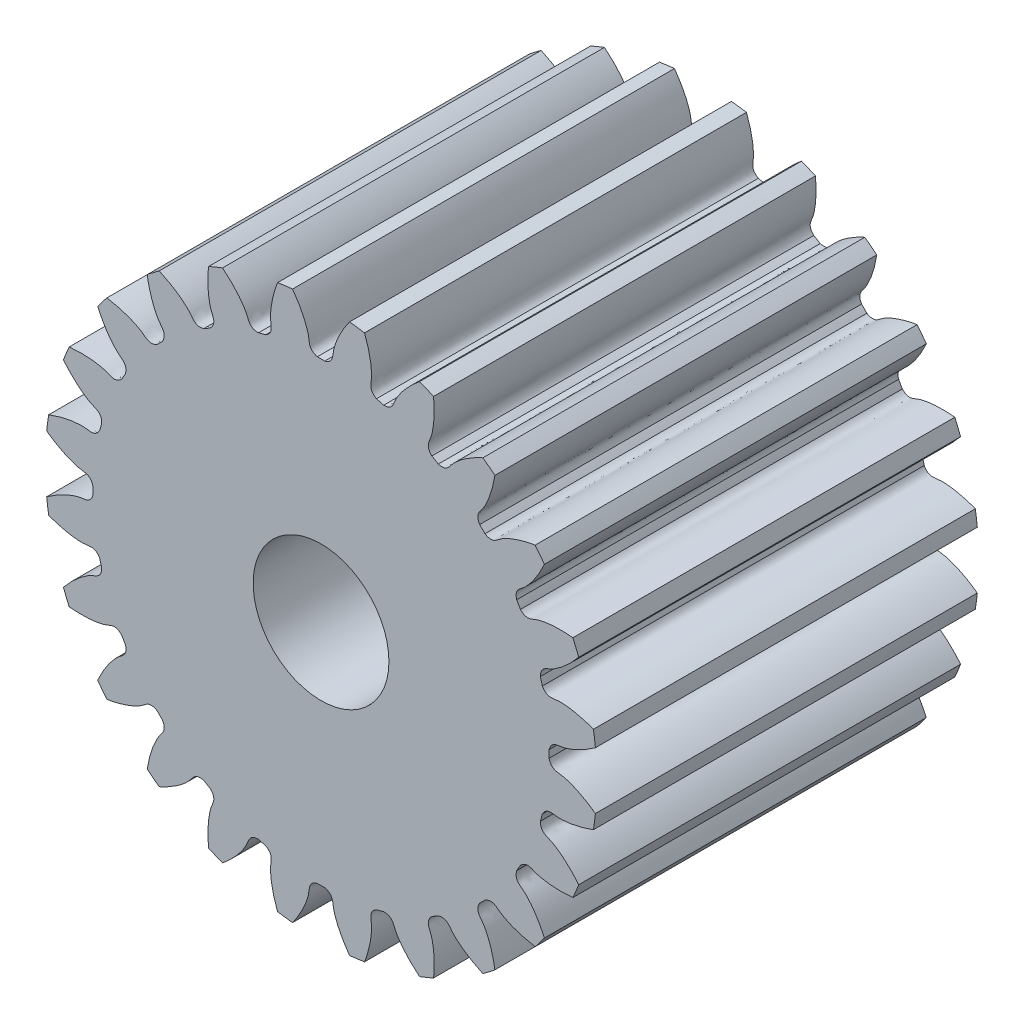
SolidWorks part; units mm, degrees
ref_plane "前视基准面" through (0, 0, 0) normal (0, 0, 1) x (1, 0, 0)
ref_plane "上视基准面" through (0, 0, 0) normal (0, 1, 0) x (1, 0, 0)
ref_plane "右视基准面" through (0, 0, 0) normal (1, 0, 0) x (0, 0, -1)
sketch "草图1" plane through (0, 0, 0) normal (0, 0, 1) x (1, 0, 0)
  circle A0 centre (0, 0) radius 6.5
extrude "凸台-拉伸1" add sketch "草图1" along normal blind 9
ref_axis "基准轴1" through (0, 0, 9) along (0, 0, -1)
sketch "草图2" plane through (0, 0, 0) normal (0, 0, 1) x (1, 0, 0)
  line L0 (0, 0) -> (0, 6.5) construction
  circle A0 centre (0, 0) radius 6.5 construction
  arc A1 (0.0884, 5.3743) -> (-0.0884, 5.3743) centre (0, 0) ccw
  arc A2 (1.5578, 7.3471) -> (-1.5578, 7.3471) centre (0, 0) ccw
  spline S0 degree 3 poles (0.0884, 5.3743) (0.284, 5.4284) (0.2695, 5.5579) (0.2931, 5.6863) (0.2965, 5.7029) (0.3007, 5.7216) (0.3058, 5.7424) (0.312, 5.7653) (0.3191, 5.7902) (0.3275, 5.8171) (0.3371, 5.846) (0.348, 5.8769) (0.3604, 5.9096) (0.3742, 5.9441) (0.3896, 5.9805) (0.4067, 6.0185) (0.4254, 6.0583) (0.446, 6.0997) (0.4684, 6.1427) (0.4928, 6.1872) (0.5192, 6.2332) (0.5476, 6.2806) (0.5782, 6.3293) (0.611, 6.3792) (0.6461, 6.4304) (0.6834, 6.4827) (0.7232, 6.536) (0.7654, 6.5903) (0.8101, 6.6456) (0.8574, 6.7016) (0.9073, 6.7583) (0.9598, 6.8158) (1.015, 6.8738) (1.0729, 6.9322) (1.1336, 6.9911) (1.1972, 7.0503) (1.2635, 7.1097) (1.3328, 7.1693) (1.4302, 7.2497) (1.506, 7.3084) (1.5578, 7.3471) knots 0 0 0 0 0.143961 0.149818 0.156577 0.164236 0.172796 0.182258 0.19262 0.203884 0.216049 0.229115 0.243082 0.25795 0.273719 0.290389 0.30796 0.326433 0.345806 0.366081 0.387257 0.409333 0.432311 0.45619 0.48097 0.506651 0.533234 0.560717 0.589101 0.618387 0.648574 0.679661 0.71165 0.74454 0.778331 0.813023 0.848616 0.885111 0.922506 1 1 1 1
  spline S1 degree 3 poles (-0.0884, 5.3743) (-0.284, 5.4284) (-0.2695, 5.5579) (-0.2931, 5.6863) (-0.2965, 5.7029) (-0.3007, 5.7216) (-0.3058, 5.7424) (-0.312, 5.7653) (-0.3191, 5.7902) (-0.3275, 5.8171) (-0.3371, 5.846) (-0.348, 5.8769) (-0.3604, 5.9096) (-0.3742, 5.9441) (-0.3896, 5.9805) (-0.4067, 6.0185) (-0.4254, 6.0583) (-0.446, 6.0997) (-0.4684, 6.1427) (-0.4928, 6.1872) (-0.5192, 6.2332) (-0.5476, 6.2806) (-0.5782, 6.3293) (-0.611, 6.3792) (-0.6461, 6.4304) (-0.6834, 6.4827) (-0.7232, 6.536) (-0.7654, 6.5903) (-0.8101, 6.6456) (-0.8574, 6.7016) (-0.9073, 6.7583) (-0.9598, 6.8158) (-1.015, 6.8738) (-1.0729, 6.9322) (-1.1336, 6.9911) (-1.1972, 7.0503) (-1.2635, 7.1097) (-1.3328, 7.1693) (-1.4302, 7.2497) (-1.506, 7.3084) (-1.5578, 7.3471) knots 0 0 0 0 0.143961 0.149818 0.156577 0.164236 0.172796 0.182258 0.19262 0.203884 0.216049 0.229115 0.243082 0.25795 0.273719 0.290389 0.30796 0.326433 0.345806 0.366081 0.387257 0.409333 0.432311 0.45619 0.48097 0.506651 0.533234 0.560717 0.589101 0.618387 0.648574 0.679661 0.71165 0.74454 0.778331 0.813023 0.848616 0.885111 0.922506 1 1 1 1
extrude "切除-拉伸1" cut sketch "草图2" along normal through all
pattern_circular "阵列(圆周)1" count 24 every 15 about axis through (0, 0, 9) along (0, 0, -1) of "切除-拉伸1"
sketch "草图3" plane through (0, 0, 0) normal (0, 0, 1) x (1, 0, 0)
  circle A0 centre (0, 0) radius 6 construction
  dimension "Dn" = 12
sketch "草图4" plane through (0, 0, 9) normal (0, 0, 1) x (1, 0, 0)
  circle A0 centre (0, 0) radius 1.6
  dimension "D1" = 3.2
extrude "切除-拉伸2" cut sketch "草图4" against normal up to next
